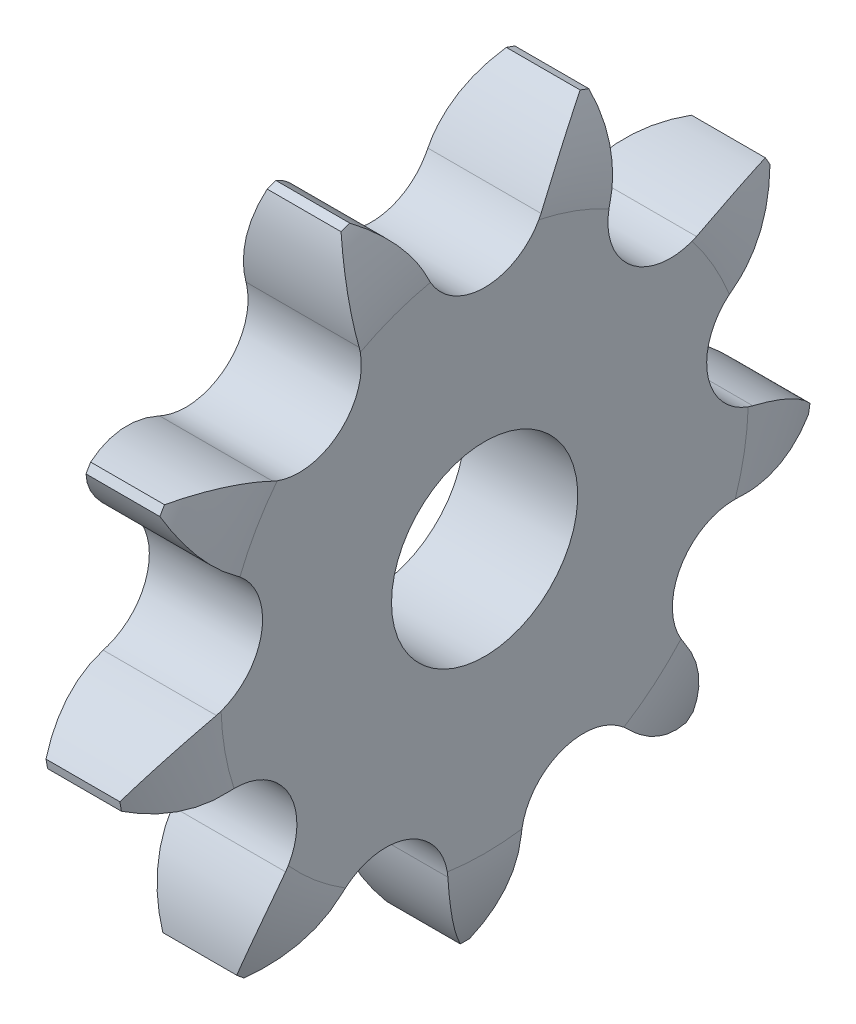
SolidWorks part; units mm, degrees
ref_plane "Plane1" through (0, 0, 0) normal (0, 0, 1) x (1, 0, 0)
ref_plane "Plane2" through (0, 0, 0) normal (0, 1, 0) x (1, 0, 0)
ref_plane "Plane3" through (0, 0, 0) normal (1, 0, 0) x (0, 0, -1)
sketch "Clipboard" plane through (0, 0, 0) normal (0, 1, 0) x (1, 0, 0)
  line L0 (0, 0) -> (12.5436, -1.9867)
  line L1 (-15, 0) -> (100, 0) construction
  line L2 (0, 0) -> (-0.8416, 0.9512)
  line L3 (0, 0) -> (-11.863, 4.5341)
  line L4 (0, 0) -> (3.0618, 0.4849)
  line L5 (0, 0) -> (-2.8109, -1.0484)
  line L6 (0, 0) -> (-6.0514, -4.0829)
  line L7 (-0.8416, 0.9512) -> (8.5146, 2.6009)
  line L8 (-76.2, 38.1) -> (-75.2, 38.1)
  line L9 (-73.4321, 41.7084) -> (-72.837, 41.7846)
  line L10 (-73.4741, 12.9512) -> (-59.0941, 12.9512)
  circle A0 centre (0, 0) radius 3.975
  circle A1 centre (0, 0) radius 10.0465
  circle A2 centre (0, 0) radius 25
  dimension "Num_teeth" = 9
  dimension "Thickness" = 7.3
sketch "BasProSke" plane through (0, 0, 0) normal (0, 1, 0) x (1, 0, 0)
  line L0 (-10, 0) -> (60, 0) construction
  line L1 (0, 0) -> (0, 16.9929)
  line L2 (0, 0) -> (7.3, 0)
  line L3 (7.3, 0) -> (7.3, 16.9929)
  line L4 (6.03, 22.5287) -> (1.27, 22.5287)
  arc A0 (0, 16.9929) -> (1.27, 22.5287) centre (12.7, 16.9929) cw
  arc A1 (7.3, 16.9929) -> (6.03, 22.5287) centre (-5.4, 16.9929) ccw
  dimension "D1" = 12.7
  dimension "Thickness" = 7.3
  dimension "Diameter" = 45.0573
revolve "Base-Revolve" add sketch "BasProSke" angle 360 about L0
sketch "TooCutSke" plane through (0, 0, 0) normal (1, 0, 0) x (0, 0, -1)
  line L0 (0, 18.6059) -> (3.6386, 16.9092) construction
  line L1 (0, 0) -> (0, 107) construction
  line L2 (0, 18.6059) -> (-10, 18.6059) construction
  line L3 (0, 18.6059) -> (-3.6386, 16.9092) construction
  arc A0 (3.6386, 16.9092) -> (7.9748, 21.6037) centre (13.1494, 12.4742) cw
  arc A1 (3.6386, 16.9092) -> (-3.6386, 16.9092) centre (0, 18.6059) cw
  arc A2 (-3.6386, 16.9092) -> (-7.9748, 21.6037) centre (-13.1494, 12.4742) ccw
  arc A3 (7.9748, 21.6037) -> (-7.9748, 21.6037) centre (0, 0) ccw
extrude "ToothCut" cut sketch "TooCutSke" along normal through all
pattern_circular "TeethCuts" count 9 every 40 about axis through (-10, 0, 0) along (1, 0, 0) of "ToothCut"
sketch "HubNeaOneSke" plane through (0, 0, 0) normal (-1, 0, 0) x (0, 0, 1)
  circle A0 centre (0, 0) radius 10.0465
  dimension "Diameter" = 20.093
extrude "HubNearOne" [suppressed] add sketch "HubNeaOneSke" along normal blind 2.2005
fillet "HubNearOneFillet" [suppressed] radius 0.6
sketch "HubNeaBotSke" plane through (0, 0, 0) normal (-1, 0, 0) x (0, 0, 1)
  circle A0 centre (0, 0) radius 10.0465
  dimension "Diameter" = 20.093
extrude "HubNearBoth" [suppressed] add sketch "HubNeaBotSke" along normal blind 1.1003
fillet "HubNearBothFillet" [suppressed] radius 0.6
ref_plane "FarPln" through (7.3, 0, 0) normal (1, 0, 0) x (0, 0, -1)
sketch "HubFarSke" plane through (7.3, 0, 0) normal (1, 0, 0) x (0, 0, -1)
  circle A0 centre (0, 0) radius 10.0465
  dimension "Diameter" = 20.093
extrude "HubFar" [suppressed] add sketch "HubFarSke" along normal blind 1.1003
fillet "HubFarFillet" [suppressed] radius 0.6
sketch "BorSke" plane through (0, 0, 0) normal (1, 0, 0) x (0, 0, -1)
  circle A0 centre (0, 0) radius 6
  dimension "Diameter" = 12
extrude "Bore" cut sketch "BorSke" along normal mid plane 19.001
sketch "KeySke" plane through (0, 0, 0) normal (1, 0, 0) x (0, 0, -1)
  line L0 (-1, 0) -> (-1, 7)
  line L1 (-1, 7) -> (1, 7)
  line L2 (1, 7) -> (1, 0)
  line L3 (0, 0) -> (0, 34) construction
  line L4 (-1, 0) -> (1, 0)
  dimension "Width" = 2
extrude "Keyway" [suppressed] cut sketch "KeySke" along normal mid plane 19.001
pattern_circular "Keyway2" [suppressed] count 2 every 90 about axis through (-10, 0, 0) along (1, 0, 0)
equation "' \"Pitch@Clipboard\" = 12.7"
equation "' \"Num_strands@Clipboard\" = 1"
equation "' \"Num_teeth@Clipboard\" = 9"
equation "' \"Hub_dia@Clipboard\" = 50"
equation "' \"Overall_len@Clipboard\" = 3"
equation "' \"Diameter@BorSke\" = 12"
equation "' \"T_dim@Clipboard\" = 1"
equation "' \"Width@KeySke\" = 2"
equation "' \"Dr@Clipboard\" = 7.95"
equation "' \"Face_width@Clipboard\" = 7.3"
equation "' \"Side_radius@Clipboard\" = 12.7"
equation "' \"Side_relief@Clipboard\" = 1.27"
equation "' \"Transv_pitch@Clipboard\" = 14.38"
equation "' \"Show_teeth@Clipboard\" = 9"
equation "' \"Fillet_rad@Clipboard\" = 0.6"
equation "' \"Plate_wid@Clipboard\" = 12"
equation "\"Num_teeth@Clipboard\" = int( \"Num_teeth@Clipboard\" )"
equation "\"Num_teeth@Clipboard\" = ((sgn( \"Num_teeth@Clipboard\" - 5.0)+1)*( \"Num_teeth@Clipboard\" - 5.0))/2 +5.0"
equation "\"Num_teeth@Clipboard\" = ((sgn( \"Num_teeth@Clipboard\" - 200.0)-1)*( \"Num_teeth@Clipboard\" - 200.0))/-2 +200.0"
equation "\"MHD@Clipboard\" = \"Pitch@Clipboard\" * (1.0 / tan(3.14159265 / \"Num_teeth@Clipboard\" )) - 1.05 * \"Plate_wid@Clipboard\" - 2.0 * \"Fillet_rad@Clipboard\" - 1.0"
equation "\"Thickness@Clipboard\"  = \"Face_width@Clipboard\" + (\"Num_strands@Clipboard\" - 1) * \"Transv_pitch@Clipboard\""
equation "\"OAL@Clipboard\" = \"Thickness@Clipboard\" + 2 * \"Fillet_rad@Clipboard\" + 1"
equation "\"MHD@Clipboard\" = ((sgn( \"MHD@Clipboard\" - \"Hub_dia@Clipboard\" )-1)*( \"MHD@Clipboard\" - \"Hub_dia@Clipboard\" ))/-2+ \"Hub_dia@Clipboard\""
equation "\"OAL@Clipboard\" = ((sgn( \"OAL@Clipboard\" - \"Overall_len@Clipboard\" )+1)*( \"OAL@Clipboard\" - \"Overall_len@Clipboard\" ))/2 + \"Overall_len@Clipboard\" + 0.0005"
equation "\"Num_teeth@TeethCuts\" = int( \"Show_teeth@Clipboard\" ) + 1"
equation "\"Num_teeth@TeethCuts\" = ((sgn( \"Num_teeth@TeethCuts\" - \"Num_teeth@Clipboard\" )-1)*( \"Num_teeth@TeethCuts\" - \"Num_teeth@Clipboard\" ))/-2+ \"Num_teeth@Clipboard\""
equation "\"Num_teeth@TeethCuts\" = ((sgn( \"Num_teeth@TeethCuts\" - 2.0)+1)*( \"Num_teeth@TeethCuts\" - 2.0))/2 +2.0"
equation "\"Angle@TeethCuts\" = 360.0 / \"Num_teeth@Clipboard\""
equation "\"Seat_radius@TooCutSke\" = ( \"Pitch@Clipboard\" / 2.0) / sin(3.14159265 / \"Num_teeth@Clipboard\" ) - \"Dr@Clipboard\" / 2.0 + \"Dr@Clipboard\" * 0.505"
equation "\"R1@TooCutSke\"  = \"Dr@Clipboard\" * 0.505"
equation "\"X@TooCutSke\" = 140.0 - (90.0 / \"Num_teeth@Clipboard\")"
equation "\"R2@TooCutSke\" = 0.12 * \"Dr@Clipboard\" * ( \"Num_teeth@Clipboard\" + 2.0)"
equation "\"Overcut@TooCutSke\" = 0.5 + 0.625 * \"Pitch@Clipboard\" - 0.5 * \"Dr@Clipboard\"  +  \"Pitch@Clipboard\" / 2.0 / sin(3.14159265 / \"Num_teeth@Clipboard\" )"
equation "\"Diameter@BasProSke\" = 2.0 * ( 0.625 * \"Pitch@Clipboard\" - 0.5 * \"Dr@Clipboard\"  +  \"Pitch@Clipboard\" / 2.0 / sin(3.14159265 / \"Num_teeth@Clipboard\" ))"
equation "\"Thickness@BasProSke\"  = \"Thickness@Clipboard\""
equation "\"G1@BasProSke\" =  \"Side_relief@Clipboard\""
equation "\"G2@BasProSke\" =  \"Side_relief@Clipboard\""
equation "\"D1@BasProSke\" =  \"Side_radius@Clipboard\""
equation "\"Diameter@HubNeaOneSke\" = \"MHD@Clipboard\""
equation "\"Length@HubNearOne\" = \"OAL@Clipboard\" - \"Thickness@BasProSke\""
equation "\"Diameter@HubNeaBotSke\" = \"MHD@Clipboard\""
equation "\"Length@HubNearBoth\" = ( \"OAL@Clipboard\" - \"Thickness@BasProSke\" ) / 2.0"
equation "\"D1@HubNearOneFillet\" = \"Fillet_rad@Clipboard\""
equation "\"D1@HubNearBothFillet\" = \"Fillet_rad@Clipboard\""
equation "\"Thickness@FarPln\" = \"Thickness@BasProSke\""
equation "\"Diameter@HubFarSke\" = \"MHD@Clipboard\""
equation "\"Length@HubFar\" = ( \"OAL@Clipboard\" - \"Thickness@BasProSke\" ) / 2.0"
equation "\"D1@HubFarFillet\" = \"Fillet_rad@Clipboard\""
equation "\"D1@Bore\" = \"OAL@Clipboard\" * 2.0"
equation "\"D1@Keyway\" = \"OAL@Clipboard\" * 2.0"
equation "\"Offset@KeySke\" = \"T_dim@Clipboard\" + \"Diameter@BorSke\" / 2.0"
